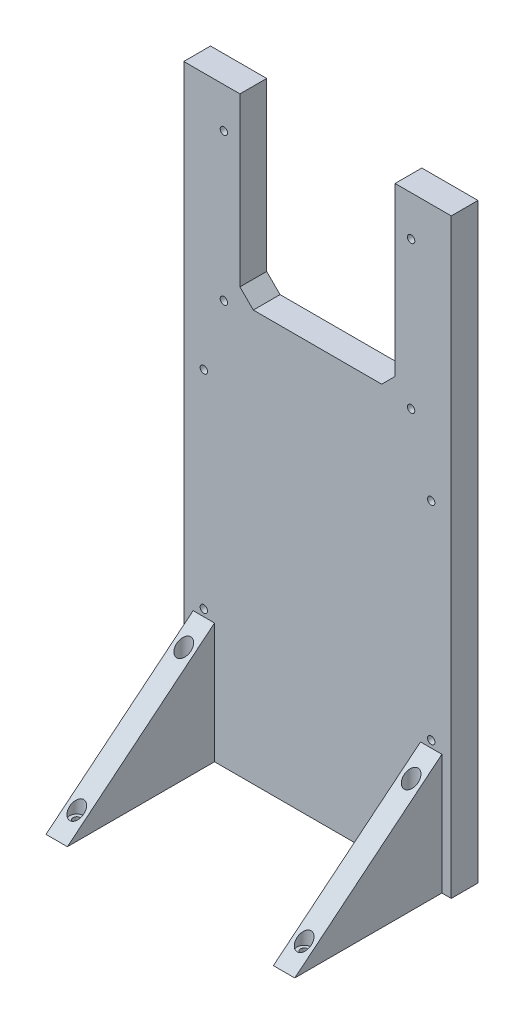
SolidWorks part; units mm, degrees
note: The reader was unsure of these and kept them because the rebuilt part matched: shared geometry of "Sketch5<3>", "Sketch1<3>".
ref_plane "Front Plane" through (0, 0, 0) normal (0, 0, 1) x (1, 0, 0)
ref_plane "Top Plane" through (0, 0, 0) normal (0, 1, 0) x (1, 0, 0)
ref_plane "Right Plane" through (0, 0, 0) normal (1, 0, 0) x (0, 0, -1)
sketch "Sketch1" plane through (0, 0, 0) normal (0, 0, 1) x (1, 0, 0)
  line L0 (-42.5, 14.5) -> (-42.5, 40.52)
  line L1 (-50, -110.5) -> (50, -110.5)
  line L2 (-50, -110.5) -> (-50, 110.5)
  line L3 (-50, 110.5) -> (50, 110.5)
  line L4 (50, -110.5) -> (50, 110.5)
  line L5 (-50, -110.5) -> (50, 110.5) construction
  line L6 (-50, 110.5) -> (50, -110.5) construction
  line L7 (-42.5, 40.52) -> (-35, 40.52)
  line L8 (0, 110.5) -> (0, -110.5)
  line L10 (0, -110.5) -> (-42.5, -110.5)
  line L12 (-42.5, -103) -> (-42.5, -63)
  line L13 (-42.5, -63) -> (-42.5, 14.5)
  line L14 (0, 110.5) -> (0, 77.1016)
  line L15 (-29, 43.01) -> (29, 43.01)
  line L16 (-29, 43.01) -> (-29, 111.1933)
  line L17 (-29, 111.1933) -> (29, 111.1933)
  line L18 (29, 43.01) -> (29, 111.1933)
  line L19 (-29, 43.01) -> (29, 111.1933) construction
  line L20 (-29, 111.1933) -> (29, 43.01) construction
  circle A10 centre (-42.5, 14.5) radius 1.375
  circle A11 centre (-42.5, -63) radius 1.375
  circle A12 centre (-42.5, -103) radius 1.375
  circle A13 centre (42.5, -63) radius 1.375
  circle A14 centre (42.5, 14.5) radius 1.375
  circle A15 centre (42.5, -103) radius 1.375
  point P0 (0, 0)
  point P30 (0, 77.1016)
  dimension "D5" = 7.5
  dimension "D1" = 100
  dimension "D4" = 221
  dimension "D6" = 58
extrude "Boss-Extrude1" add sketch "Sketch1" along normal blind 10
chamfer "Chamfer1" distance 5 angle 45 2 edges at (-29, 43.01, 5) (29, 43.01, 5)
sketch "Sketch2" plane through (0, 0, 10) normal (0, 0, 1) x (1, 0, 0)
  line L0 (-42.5, -64.375) -> (-42.5, -101.625) construction
  line L1 (-50, -110.5) -> (50, -110.5) construction
  line L2 (-46.5, -55.5) -> (-38.5, -55.5)
  line L3 (-46.5, -55.5) -> (-46.5, -110.5)
  line L4 (-46.5, -110.5) -> (-38.5, -110.5)
  line L5 (-38.5, -55.5) -> (-38.5, -110.5)
  line L6 (-46.5, -55.5) -> (-38.5, -110.5) construction
  line L7 (-46.5, -110.5) -> (-38.5, -55.5) construction
  line L8 (0, -110.5) -> (0, 110.5)
  line L9 (-50, 110.5) -> (-29, 110.5) construction
  line L10 (46.5, -110.5) -> (38.5, -110.5)
  line L11 (38.5, -55.5) -> (38.5, -110.5)
  line L12 (46.5, -55.5) -> (38.5, -55.5)
  line L13 (46.5, -55.5) -> (46.5, -110.5)
  line L14 (46.5, -65.5) -> (38.5, -65.5)
  line L15 (-46.5, -55.5) -> (-38.5, -55.5)
  line L16 (-46.5, -55.5) -> (-46.5, -65.5)
  line L17 (-46.5, -65.5) -> (-38.5, -65.5)
  line L18 (-38.5, -55.5) -> (-38.5, -65.5)
  line L19 (38.5, -55.5) -> (38.5, -65.5)
  line L20 (46.5, -55.5) -> (38.5, -55.5)
  line L21 (46.5, -55.5) -> (46.5, -65.5)
  circle A0 centre (-42.5, -63) radius 1.375 construction
  circle A1 centre (-42.5, -103) radius 1.375 construction
  point P7 (-42.5, -83)
  dimension "D1" = 8
  dimension "D2" = 10
extrude "Boss-Extrude2" add sketch "Sketch2" along normal blind 55
sketch "Sketch5" plane through (0, -55.5, 0) normal (0, 1, 0) x (1, 0, 0)
  line L0 (-42.5, -57.5) -> (-42.5, -17.5)
  line L1 (42.5, -57.5) -> (42.5, -17.5)
  circle A0 centre (-42.5, -17.5) radius 1.375
  circle A1 centre (-42.5, -57.5) radius 1.375
  circle A2 centre (42.5, -17.5) radius 1.375
  circle A3 centre (42.5, -57.5) radius 1.375
  circle A4 centre (-42.5, -17.5) radius 2.6
  circle A5 centre (-42.5, -57.5) radius 2.6
  circle A6 centre (42.5, -17.5) radius 2.6
  circle A7 centre (42.5, -57.5) radius 2.6
  point P3 (-42.5, -37.5)
  point P6 (42.5, -37.5)
extrude "Cut-Extrude2" cut sketch "Sketch5" against normal through all contours A0 | A1 | A3 | A2
extrude "Cut-Extrude3" cut sketch "Sketch5<3>" against normal offset from surface (52 mm away) 3 contours A4 | A5 | A7 | A6 up to face at (42.5, -110.5, 18.875)
sketch "Sketch5<3>" plane through (0, -55.5, 0) normal (0, 1, 0) x (1, 0, 0) same geometry as "Sketch5"
extrude "Cut-Extrude4" cut sketch "Sketch1<3>" along normal blind 10 contours A15 | A12
sketch "Sketch1<3>" plane through (0, 0, 0) normal (0, 0, 1) x (1, 0, 0) same geometry as "Sketch1"
chamfer "Chamfer3" distance 45 angle 50.75 2 edges at (42.5, -65.5, 65) (-42.5, -65.5, 65)
sketch "Sketch6" plane through (0, 0, 10) normal (0, 0, 1) x (1, 0, 0)
  circle A0 centre (-35, 95.5) radius 1.375
  circle A1 centre (35, 95.5) radius 1.375
  circle A2 centre (35, 40.52) radius 1.375
  circle A3 centre (-35, 40.52) radius 1.375
extrude "Cut-Extrude5" cut sketch "Sketch6" against normal up to surface (10 mm away) up to face at (43.875, -63, 0)
